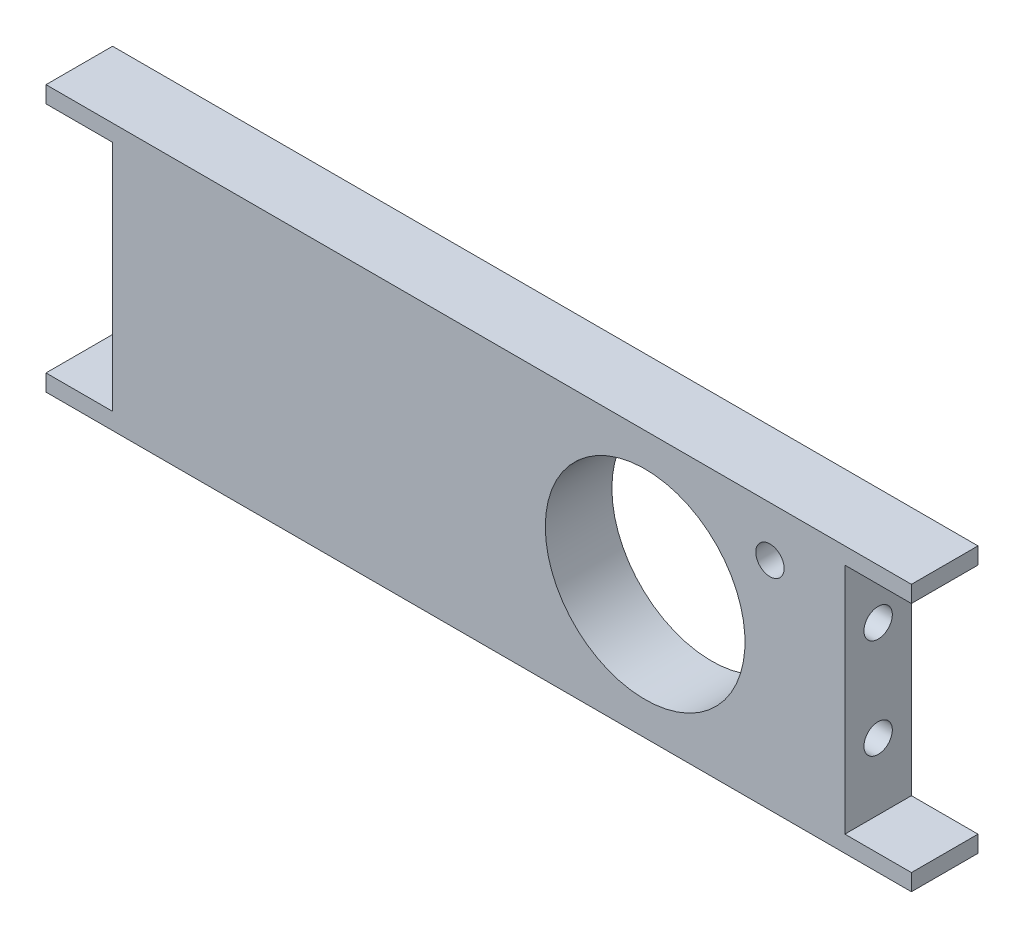
SolidWorks part; units mm, degrees
material "6061-T6 (SS)"
ref_plane "Front" through (0, 0, 0) normal (0, 0, 1) x (1, 0, 0)
ref_plane "Top" through (0, 0, 0) normal (0, 1, 0) x (1, 0, 0)
ref_plane "Right" through (0, 0, 0) normal (1, 0, 0) x (0, 0, -1)
sketch "Sketch1" plane through (0, 0, 0) normal (0, 0, 1) x (1, 0, 0)
  line L0 (0, 12.7) -> (0, -12.7) construction
  line L1 (-41.275, -12.7) -> (41.275, -12.7)
  line L2 (-41.275, -12.7) -> (-41.275, -11.1125)
  line L3 (-41.275, 12.7) -> (41.275, 12.7)
  line L4 (41.275, -12.7) -> (41.275, -11.1125)
  line L5 (-41.275, -12.7) -> (41.275, 12.7) construction
  line L6 (-41.275, 12.7) -> (41.275, -12.7) construction
  line L7 (-41.275, 11.1125) -> (-34.925, 11.1125)
  line L8 (41.275, 11.1125) -> (41.275, 12.7)
  line L9 (-41.275, -11.1125) -> (-34.925, -11.1125)
  line L10 (-34.925, 11.1125) -> (-34.925, -11.1125)
  line L11 (41.275, -11.1125) -> (34.925, -11.1125)
  line L12 (41.275, 11.1125) -> (34.925, 11.1125)
  line L13 (34.925, 11.1125) -> (34.925, -11.1125)
  line L14 (-41.275, 11.1125) -> (-41.275, 12.7)
  point P0 (0, 0)
  dimension "D1" = 82.55
  dimension "D2" = 25.4
  dimension "D3" = 1.5875
  dimension "D4" = 1.5875
  dimension "D5" = 6.35
extrude "Boss-Extrude1" add sketch "Sketch1" along normal blind 6.35
hole_wizard "Tap Drill for #6-32 Tap1" positions "Sketch3" profile "Sketch4" hole size "#6-32" standard "ANSI Inch"
sketch "Sketch3" plane through (34.925, 0, 0) normal (1, 0, 0) x (0, 0, -1)
  line L0 (-6.35, 12.7) -> (0, 12.7) construction
  line L1 (-6.35, -12.7) -> (0, -12.7) construction
  line L2 (-6.35, -11.1125) -> (0, -11.1125) construction
  point P0 (-3.175, 4.7625)
  point P2 (-3.175, -4.7625)
  point P12 (-3.175, -11.1125)
  dimension "D1" = 7.9375
  dimension "D2" = 7.9375
sketch "Sketch4" plane through (34.925, 4.7625, 3.175) normal (0, 1, 0) x (0, 0, -1)
  line L0 (0, 0) -> (0, 7.1627)
  line L1 (0, 7.1627) -> (1.3525, 6.35)
  line L2 (1.3525, 6.35) -> (1.3525, 0)
  line L5 (1.3525, 0) -> (0, 0)
  line L10 (0, 7.1627) -> (-1.3525, 6.35) construction
  line L11 (0, -6.35) -> (0, 107.95) construction
  dimension "Hole Dia." = 2.7051
  dimension "Hole Depth" = 6.35
  dimension "Drill Angle" = 118
ref_plane "Plane1" through (0, 0, 0) normal (-1, 0, 0) x (0, 0, 1)
mirror "Mirror1" about plane through (0, 0, 0) normal (-1, 0, 0) of "Tap Drill for #6-32 Tap1"
sketch "Sketch5" plane through (0, 0, 0) normal (0, 0, -1) x (-1, 0, 0)
  line L1 (-34.925, -11.1125) -> (-34.925, 11.1125) construction
  circle A1 centre (-15.875, 0) radius 9.525
  dimension "D1" = 19.05
  dimension "D3" = 19.05
extrude "Cut-Extrude1" cut sketch "Sketch5" against normal through all
hole_wizard "Tap Drill for #6-32 Tap2" positions "Sketch7" profile "Sketch6" hole size "#6-32" standard "ANSI Inch" end condition through all
sketch "Sketch7" plane through (0, 0, 0) normal (0, 0, -1) x (-1, 0, 0)
  line L0 (-41.275, 12.7) -> (41.275, 12.7) construction
  line L1 (-34.925, -11.1125) -> (-34.925, 11.1125) construction
  point P0 (-27.7812, 7.9375)
  dimension "D1" = 4.7625
  dimension "D2" = 7.1437
sketch "Sketch6" plane through (27.7812, 7.9375, 0) normal (1, 0, 0) x (0, 1, 0)
  line L0 (0, 0) -> (0, 6.35)
  line L1 (0, 6.35) -> (1.3525, 6.35)
  line L2 (1.3525, 6.35) -> (1.3525, 0)
  line L5 (1.3525, 0) -> (0, 0)
  line L11 (0, -6.35) -> (0, 107.95) construction
  dimension "Thru Hole Dia." = 2.7051
  dimension "Thru Hole Depth" = 6.35
